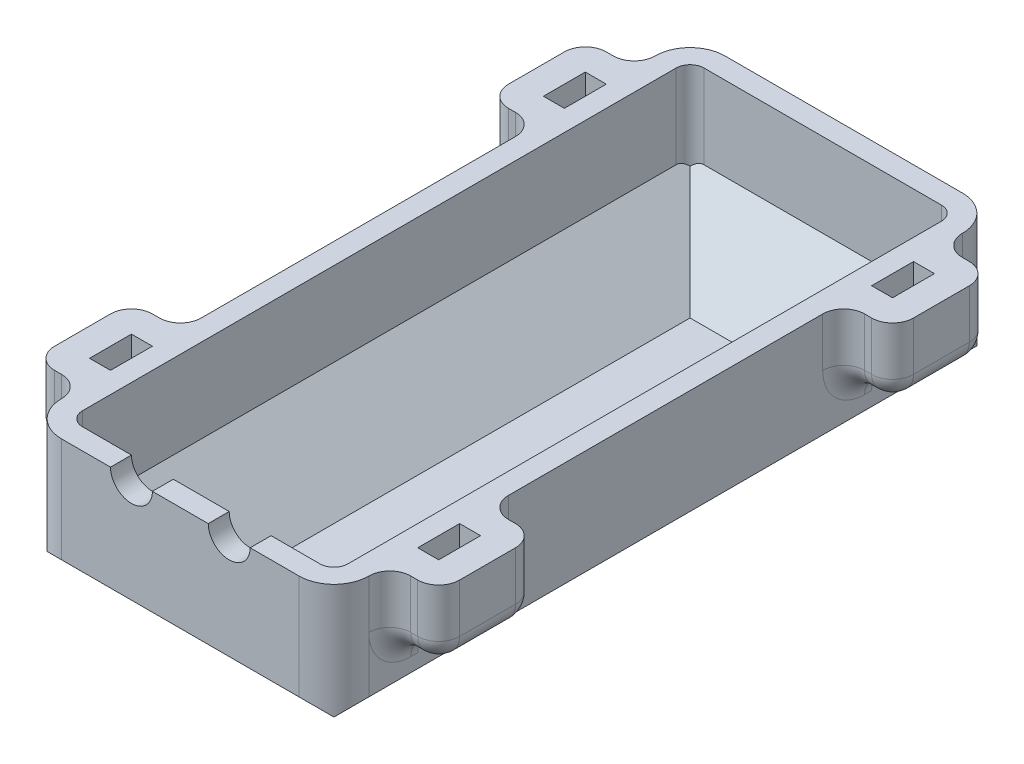
SolidWorks part; units mm, degrees
ref_plane "Front Plane" through (0, 0, 0) normal (0, 0, 1) x (1, 0, 0)
ref_plane "Top Plane" through (0, 0, 0) normal (0, 1, 0) x (1, 0, 0)
ref_plane "Right Plane" through (0, 0, 0) normal (1, 0, 0) x (0, 0, -1)
sketch "Sketch1" plane through (0, 0, 0) normal (0, 1, 0) x (1, 0, 0)
  line L1 (-22, -47.5) -> (22, -47.5)
  line L2 (-22, -47.5) -> (-22, 47.5)
  line L3 (-22, 47.5) -> (22, 47.5)
  line L4 (22, -47.5) -> (22, 47.5)
  line L5 (-22, -47.5) -> (22, 47.5) construction
  line L6 (-22, 47.5) -> (22, -47.5) construction
  point P0 (0, 0)
  dimension "D1" = 95
  dimension "D2" = 44
extrude "Boss-Extrude1" add sketch "Sketch1" along normal blind 25
sketch "Sketch2" plane through (0, 25, 0) normal (0, 1, 0) x (1, 0, 0)
  line L1 (19, -44.5) -> (-19, -44.5)
  line L2 (19, -44.5) -> (19, 44.5)
  line L3 (19, 44.5) -> (-19, 44.5)
  line L4 (-19, -44.5) -> (-19, 44.5)
  line L5 (19, -44.5) -> (-19, 44.5) construction
  line L6 (19, 44.5) -> (-19, -44.5) construction
  point P0 (0, 0)
  dimension "D1" = 89
  dimension "D2" = 38
extrude "Cut-Extrude1" cut sketch "Sketch2" against normal blind 22
chamfer "Chamfer1" distance 10 angle 45 8 edges at (0, 0, -47.5) (-22, 0, 0) (0, 0, 47.5) (22, 0, 0) (0, 3, -44.5) (19, 3, 0) (0, 3, 44.5) (-19, 3, 0)
fillet "Fillet1" radius 2 4 edges at (-19, 19, 44.5) (19, 19, 44.5) (19, 19, -44.5) (-19, 19, -44.5)
fillet "Fillet2" radius 5 4 edges at (22, 17.5, -47.5) (22, 17.5, 47.5) (-22, 17.5, 47.5) (-22, 17.5, -47.5)
sketch "Sketch3" plane through (22, 0, 0) normal (1, 0, 0) x (0, 0, -1)
  line L0 (-42.5, 25) -> (42.5, 25) construction
  line L1 (-25.5, 15) -> (-39.5, 15)
  line L2 (-25.5, 15) -> (-25.5, 25)
  line L3 (-25.5, 25) -> (-39.5, 25)
  line L4 (-39.5, 15) -> (-39.5, 25)
  line L5 (-25.5, 15) -> (-39.5, 25) construction
  line L6 (-25.5, 25) -> (-39.5, 15) construction
  line L7 (-42.5, 25) -> (-42.5, 10) construction
  line L8 (0, 25) -> (0, 10) construction
  line L9 (-29.5, 17.8571) -> (-35.5, 17.8571) construction
  line L10 (-29.5, 17.8571) -> (-29.5, 22.1429) construction
  line L11 (-29.5, 22.1429) -> (-35.5, 22.1429) construction
  line L12 (-35.5, 17.8571) -> (-35.5, 22.1429) construction
  line L13 (-29.5, 17.8571) -> (-35.5, 22.1429) construction
  line L14 (-29.5, 22.1429) -> (-35.5, 17.8571) construction
  line L15 (-42.5, 10) -> (42.5, 10) construction
  line L16 (25.5, 25) -> (39.5, 25)
  line L17 (29.5, 22.1429) -> (35.5, 17.8571) construction
  line L18 (29.5, 17.8571) -> (35.5, 22.1429) construction
  line L19 (35.5, 17.8571) -> (35.5, 22.1429) construction
  line L20 (29.5, 22.1429) -> (35.5, 22.1429) construction
  line L21 (29.5, 17.8571) -> (29.5, 22.1429) construction
  line L22 (29.5, 17.8571) -> (35.5, 17.8571) construction
  line L23 (25.5, 25) -> (39.5, 15) construction
  line L24 (25.5, 15) -> (39.5, 25) construction
  line L25 (39.5, 15) -> (39.5, 25)
  line L26 (25.5, 15) -> (25.5, 25)
  line L27 (25.5, 15) -> (39.5, 15)
  point P0 (-32.5, 20)
  point P9 (-32.5, 20)
  point P26 (32.5, 20)
  dimension "D1" = 3
  dimension "D2" = 14
  dimension "D3" = 10
  dimension "D4" = 6
extrude "Boss-Extrude2" add sketch "Sketch3" along normal blind 7
sketch "Sketch5" plane through (-22, 0, 0) normal (-1, 0, 0) x (0, 0, 1)
  line L0 (-42.5, 25) -> (42.5, 25) construction
  line L1 (25.5, 15) -> (39.5, 15)
  line L2 (25.5, 15) -> (25.5, 25)
  line L3 (25.5, 25) -> (39.5, 25)
  line L4 (39.5, 15) -> (39.5, 25)
  line L5 (25.5, 15) -> (39.5, 25) construction
  line L6 (25.5, 25) -> (39.5, 15) construction
  line L7 (42.5, 10) -> (42.5, 25) construction
  line L8 (0, 25) -> (0, 10) construction
  line L9 (-42.5, 10) -> (42.5, 10) construction
  line L10 (-39.5, 15) -> (-39.5, 25)
  line L11 (-25.5, 25) -> (-39.5, 15) construction
  line L12 (-25.5, 15) -> (-39.5, 25) construction
  line L13 (-25.5, 25) -> (-39.5, 25)
  line L14 (-25.5, 15) -> (-25.5, 25)
  line L15 (-25.5, 15) -> (-39.5, 15)
  point P0 (32.5, 20)
  point P17 (-32.5, 20)
  dimension "D1" = 10
  dimension "D2" = 14
  dimension "D3" = 3
extrude "Boss-Extrude3" add sketch "Sketch5" along normal blind 7
fillet "Fillet3" radius 3 32 edges at (29, 20, 25.5) (29, 15, 32.5) (29, 20, 39.5) (29, 20, -25.5) (29, 15, -32.5) (29, 20, -39.5) (-29, 20, 39.5) (-29, 15, 32.5) (-29, 20, 25.5) (-29, 20, -25.5) (-29, 15, -32.5) (-29, 20, -39.5) (25.5, 15, 25.5) (25.5, 15, 39.5) (25.5, 15, -25.5) (25.5, 15, -39.5) (-25.5, 15, 39.5) (-25.5, 15, 25.5) (-25.5, 15, -25.5) (-25.5, 15, -39.5) (-22, 20, -39.5) (22, 20, 39.5) (22, 20, 25.5) (22, 20, -25.5) (22, 20, -39.5) (-22, 20, 25.5) (-22, 20, 39.5) (-22, 15, -32.5) (22, 15, 32.5) (22, 15, -32.5) (-22, 15, 32.5) (-22, 20, -25.5)
sketch "Sketch7" plane through (0, 25, 0) normal (0, 1, 0) x (1, 0, 0)
  line L0 (-26, 39.5) -> (-25, 39.5) construction
  line L13 (-25, 35.5) -> (-22, 35.5)
  line L14 (-25, 35.5) -> (-25, 29.5)
  line L15 (-25, 29.5) -> (-22, 29.5)
  line L16 (-22, 35.5) -> (-22, 29.5)
  line L17 (0, 47.5) -> (0, -19.4636) construction
  line L18 (17, 47.5) -> (-17, 47.5) construction
  line L19 (-22, 0) -> (22, 0) construction
  line L20 (-22, 22.5) -> (-22, -22.5) construction
  line L21 (22, -22.5) -> (22, 22.5) construction
  line L22 (22, 35.5) -> (22, 29.5)
  line L23 (25, 29.5) -> (22, 29.5)
  line L24 (25, 35.5) -> (25, 29.5)
  line L25 (25, 35.5) -> (22, 35.5)
  line L26 (25, -35.5) -> (22, -35.5)
  line L27 (25, -35.5) -> (25, -29.5)
  line L28 (25, -29.5) -> (22, -29.5)
  line L29 (22, -35.5) -> (22, -29.5)
  line L30 (-22, -35.5) -> (-22, -29.5)
  line L31 (-25, -29.5) -> (-22, -29.5)
  line L32 (-25, -35.5) -> (-25, -29.5)
  line L33 (-25, -35.5) -> (-22, -35.5)
  dimension "D1" = 4
  dimension "D2" = 3
  dimension "D3" = 6
extrude "Cut-Extrude2" cut sketch "Sketch7" against normal through all and the other way through all
sketch "Sketch8" plane through (0, 0, 47.5) normal (0, 0, 1) x (1, 0, 0)
  line L1 (-17, 25) -> (17, 25) construction
  line L2 (0, 25) -> (0, 28.187) construction
  circle A2 centre (7, 25) radius 3
  circle A3 centre (-7, 25) radius 3
  dimension "D1" = 6
  dimension "D2" = 7
extrude "Cut-Extrude3" cut sketch "Sketch8" against normal blind 10
